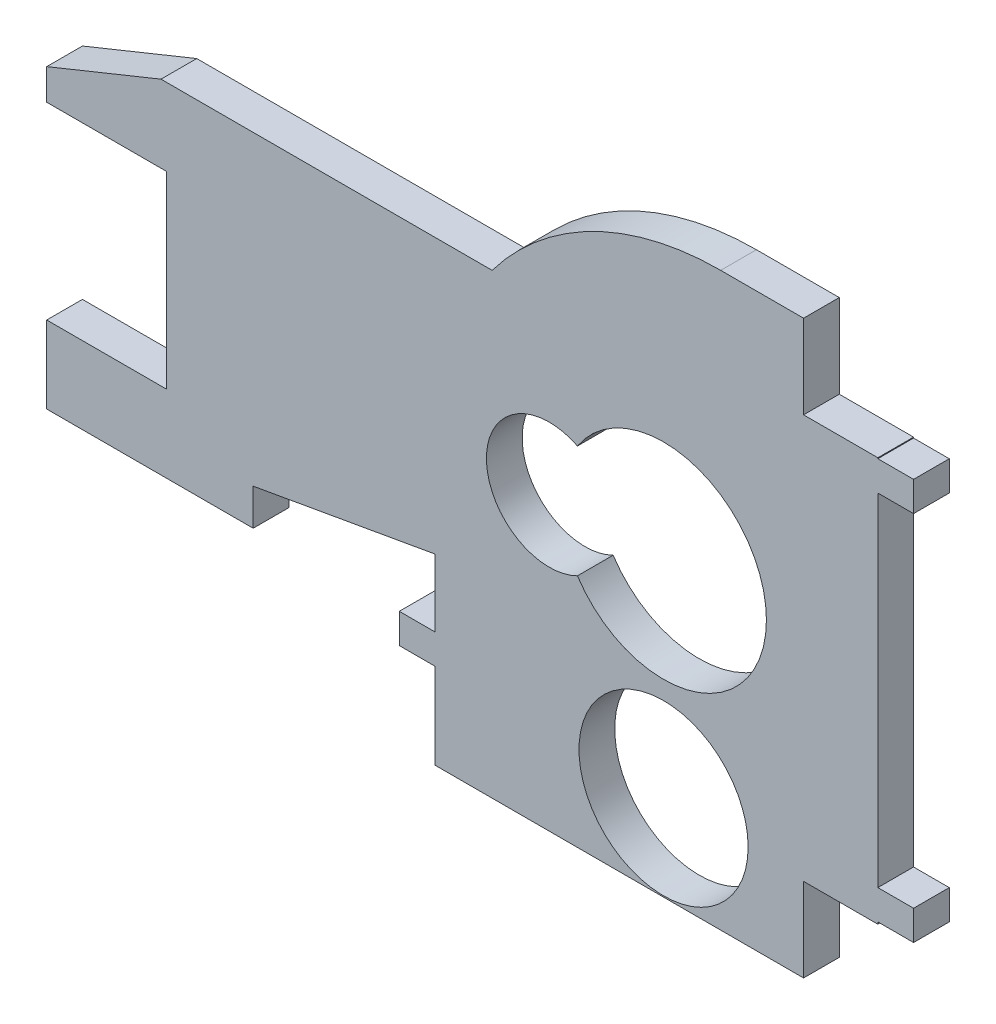
SolidWorks part; units mm, degrees
material "Balsa"
ref_plane "Front Plane" through (0, 0, 0) normal (0, 0, 1) x (1, 0, 0)
ref_plane "Top Plane" through (0, 0, 0) normal (0, 1, 0) x (1, 0, 0)
ref_plane "Right Plane" through (0, 0, 0) normal (1, 0, 0) x (0, 0, -1)
sketch "Sketch1" plane through (0, 0, 0) normal (0, 0, 1) x (1, 0, 0)
  line L0 (0, -1000.1535) -> (0, 48999.8465) construction
  line L1 (0, 9.144) -> (-5.08, 9.144) construction
  line L2 (-1000, 0) -> (49000, 0) construction
  line L3 (9.525, 16.51) -> (11.1125, 16.51)
  line L4 (2.54, 21.59) -> (9.525, 21.59)
  line L5 (-10.16, 8.89) -> (-10.16, -3.81)
  line L6 (-10.16, -3.81) -> (9.525, -3.81)
  line L7 (9.525, 21.59) -> (9.525, -3.81)
  line L8 (-11.7475, 0) -> (-10.16, 0)
  line L9 (-11.7475, 0) -> (-11.7475, 1.3208)
  line L10 (-11.7475, 1.3208) -> (-10.16, 1.3208)
  line L11 (-10.16, 0) -> (-10.16, 1.3208)
  line L12 (9.525, 0) -> (11.1125, 0)
  line L13 (9.525, 0) -> (9.525, 1.3208)
  line L14 (9.525, 1.3208) -> (11.1125, 1.3208)
  line L15 (11.1125, 0) -> (11.1125, 1.3208)
  line L16 (9.525, 16.51) -> (9.525, 17.8308)
  line L17 (9.525, 17.8308) -> (11.1125, 17.8308)
  line L18 (11.1125, 16.51) -> (11.1125, 17.8308)
  line L19 (-7.62, 16.51) -> (-27.4189, 16.51)
  line L20 (-27.4189, 16.51) -> (-27.4189, 1.27)
  line L21 (-27.4189, 1.27) -> (-10.16, 4.318)
  line L22 (9.525, 8.89) -> (-35.5862, 8.89) construction
  line L23 (-27.4189, 1.27) -> (-18.2418, 1.27)
  line L24 (-27.4189, 13.081) -> (-22.0849, 13.081)
  line L25 (-27.4189, 13.081) -> (-27.4189, 4.699)
  line L26 (-27.4189, 4.699) -> (-22.0849, 4.699)
  line L27 (-22.0849, 13.081) -> (-22.0849, 4.699)
  line L28 (-18.2418, 1.27) -> (-18.2418, 2.8907)
  line L29 (-27.4189, 14.4526) -> (-22.3389, 16.51)
  circle A0 centre (0, 0) radius 3.7592
  arc A1 (-3.829, 6.6457) -> (-3.829, 11.6423) centre (0, 9.144) ccw
  arc A2 (-3.829, 11.6423) -> (-3.829, 6.6457) centre (-5.08, 9.144) ccw
  arc A3 (2.54, 21.59) -> (-10.16, 8.89) centre (2.54, 8.89) ccw
  point P33 (9.525, 8.89)
  point P35 (-27.4189, 8.89)
  point P41 (-27.4189, 8.89)
  dimension "D1" = 7.5184
  dimension "D4" = 3.81
  dimension "D3" = 9.144
  dimension "D5" = 2.794
  dimension "D9" = 12.7
  dimension "D10" = 1.5875
  dimension "D2" = 25.4
  dimension "D6" = 9.525
  dimension "D7" = 5.08
  dimension "D8" = 19.685
  dimension "D11" = 9.144
  dimension "D12" = 1.3208
  dimension "D13" = 1.3208
  dimension "D14" = 1.5875
  dimension "D15" = 2
  dimension "D16" = 8.128
  dimension "D17" = 15.24
  dimension "D18" = 17.526
  dimension "D19" = 8.382
  dimension "D20" = 5.334
  dimension "D21" = 5.08
  dimension "D22" = 2.0574
extrude "Boss-Extrude1" add sketch "Sketch1" along normal blind 1.5875 contours L4 A3 L5 L6 L7 A0 A2 A1 | L10 L9 L8 L5 | L3 L18 L17 L7 | L12 L15 L14 L7 | A3 L19 L20 L21 L5 | L23 L28 L21 region at (10.3187, 17.1704, 0) region at (9.2036, 8.9154, 0) region at (10.3187, 0.6604, 0) region at (-17.3124, 9.7864, 0) region at (-10.9538, 0.6604, 0) region at (-21.3008, 1.8102, 0)
sketch "Sketch2" plane through (0, 0, 1.5875) normal (0, 0, 1) x (1, 0, 0)
  line L0 (9.525, -0.9144) -> (9.525, -3.0226) construction
  line L1 (6.223, -3.8481) -> (9.525, -3.8481)
  line L2 (6.223, -3.8481) -> (6.223, -0.0889)
  line L3 (6.223, -0.0889) -> (9.525, -0.0889)
  line L4 (9.525, -3.8481) -> (9.525, -0.0889)
  line L5 (9.525, -0.9144) -> (9.525, -3.0226)
  line L6 (9.525, 20.8026) -> (9.525, 18.6944) construction
  line L7 (9.525, 20.8026) -> (9.525, 18.6944)
  line L9 (6.223, 17.8689) -> (9.525, 17.8689)
  line L10 (6.223, 17.8689) -> (6.223, 21.6281)
  line L11 (6.223, 21.6281) -> (9.525, 21.6281)
  line L12 (9.525, 17.8689) -> (9.525, 21.6281)
  point P8 (9.525, -1.9685)
  point P9 (9.525, -1.9685)
  point P10 (9.525, 19.7485)
  point P15 (9.525, 19.7485)
  line M4 (9.525, 21.59) -> (2.54, 21.59)
  line M11 (-10.16, -3.81) -> (9.525, -3.81)
  line M12 (9.525, -3.81) -> (9.525, 0)
  line M20 (9.525, 17.8308) -> (9.525, 21.59)
  dimension "D1" = 3.7592
  dimension "D2" = 3.302
  dimension "D3" = 3.7592
  dimension "D4" = 3.302
extrude "Cut-Extrude1" cut sketch "Sketch2" against normal up to next contours L3 L2 L4 M11 M12 | L10 L9 M20 M4 region at (7.874, -1.9495, 1.5875) region at (7.874, 19.7294, 1.5875)
move or copy body "Body-Move/Copy1" [suppressed] bodies to move or copy 102
